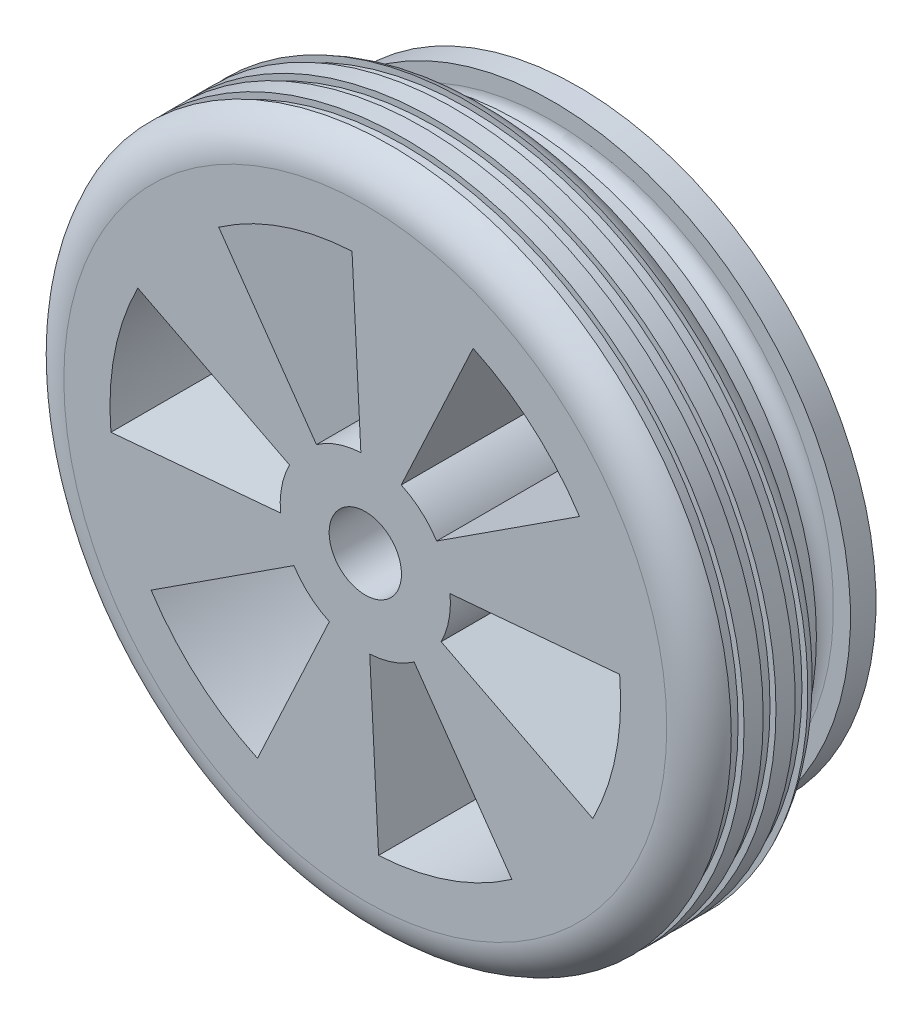
SolidWorks part; units mm, degrees
ref_plane "Plan de face" through (0, 0, 0) normal (0, 0, 1) x (1, 0, 0)
ref_plane "Plan de dessus" through (0, 0, 0) normal (0, 1, 0) x (1, 0, 0)
ref_plane "Plan de droite" through (0, 0, 0) normal (1, 0, 0) x (0, 0, -1)
sketch "Esquisse1" plane through (0, 0, 0) normal (0, 0, 1) x (1, 0, 0)
  circle A0 centre (0, 0) radius 40
  dimension "D1" = 80
extrude "Boss.-Extru.1" add sketch "Esquisse1" along normal blind 15
sketch "Esquisse2" plane through (0, 0, 0) normal (0, 0, -1) x (-1, 0, 0)
  circle A0 centre (0, 0) radius 9.65
  dimension "D1" = 19.3
extrude "Enlèv. mat.-Extru.1" cut sketch "Esquisse2" against normal blind 10.5
sketch "Esquisse3" plane through (0, 0, 10.5) normal (0, 0, -1) x (-1, 0, 0)
  circle A0 centre (0, 0) radius 4.25
  dimension "D1" = 8.5
extrude "Enlèv. mat.-Extru.2" cut sketch "Esquisse3" against normal up to next
ref_plane "Plan1" through (0, 0, 7.5) normal (0, 0, 1) x (1, 0, 0)
sketch "Esquisse4" plane through (0, 0, 7.5) normal (0, 0, 1) x (1, 0, 0)
  circle A0 centre (0, 0) radius 40
  circle A1 centre (0, 0) radius 40 construction
  circle A2 centre (0, 0) radius 39.3
  dimension "D1" = 78.6
extrude "Enlèv. mat.-Extru.4" cut sketch "Esquisse4" against normal blind 0.75 and the other way blind 0.75
ref_plane "Plan2" through (0, 0, 11.25) normal (0, 0, 1) x (1, 0, 0)
sketch "Esquisse5" plane through (0, 0, 11.25) normal (0, 0, 1) x (1, 0, 0)
  circle A1 centre (0, 0) radius 39.3
  circle A2 centre (0, 0) radius 39.3
  circle A3 centre (0, 0) radius 40
  circle A4 centre (0, 0) radius 40
  dimension "D1" = 0
  dimension "D2" = 0
extrude "Enlèv. mat.-Extru.5" cut sketch "Esquisse5" against normal blind 0.75 and the other way blind 0.75
ref_plane "Plan3" through (0, 0, 3.75) normal (0, 0, -1) x (-1, 0, 0)
sketch "Esquisse6" plane through (0, 0, 3.75) normal (0, 0, -1) x (-1, 0, 0)
  circle A1 centre (0, 0) radius 39.3
  circle A2 centre (0, 0) radius 39.3
  circle A3 centre (0, 0) radius 40
  circle A4 centre (0, 0) radius 40
  dimension "D1" = 0
  dimension "D2" = 0
extrude "Enlèv. mat.-Extru.6" cut sketch "Esquisse6" against normal blind 0.75 and the other way blind 0.75
fillet "Congé1" radius 5 2 edges at (40, 0, 0) (40, 0, 15)
sketch "Esquisse12" plane through (0, 0, 0) normal (0, 0, -1) x (-1, 0, 0)
  circle A0 centre (0, 0) radius 35
  dimension "D1" = 70
extrude "Boss.-Extru.8" add sketch "Esquisse12" along normal blind 10
sketch "Esquisse8" plane through (0, 0, 10.5) normal (0, 0, -1) x (-1, 0, 0)
  circle A0 centre (0, 0) radius 9.65
extrude "Boss.-Extru.2" add sketch "Esquisse8" along normal up to surface (10.5 mm away) up to face at (35, 0, 0)
sketch "Esquisse13" plane through (0, 0, 15) normal (0, 0, 1) x (1, 0, 0)
  circle A0 centre (0, 0) radius 4.25
extrude "Enlèv. mat.-Extru.10" cut sketch "Esquisse13" against normal up to surface (25 mm away) up to face at (-35, 0, -10)
sketch "Esquisse15" plane through (0, 0, -10) normal (0, 0, -1) x (-1, 0, 0)
  line L0 (0, 0) -> (-1.5592, -29.9595) construction
  line L1 (-1.5592, -29.9595) -> (0, 0) construction
  line L2 (0, 0) -> (-17.2184, -24.5668) construction
  line L3 (-1.5592, -29.9595) -> (-0.5197, -9.9865)
  line L4 (-17.2184, -24.5668) -> (-5.7395, -8.1889)
  line L5 (-26.7252, -13.6295) -> (-8.9084, -4.5432)
  line L6 (-29.8847, 2.6282) -> (-9.9616, 0.8761)
  line L7 (-25.1661, 16.33) -> (-8.3887, 5.4433)
  line L8 (-12.6662, 27.195) -> (-4.2221, 9.065)
  line L9 (1.5592, 29.9595) -> (0.5197, 9.9865)
  line L10 (17.2184, 24.5668) -> (5.7395, 8.1889)
  line L11 (26.7252, 13.6295) -> (8.9084, 4.5432)
  line L12 (29.8847, -2.6282) -> (9.9616, -0.8761)
  line L13 (25.1661, -16.33) -> (8.3887, -5.4433)
  line L14 (12.6662, -27.195) -> (4.2221, -9.065)
  circle A0 centre (0, 0) radius 10 construction
  circle A1 centre (0, 0) radius 30 construction
  arc A2 (-5.7395, -8.1889) -> (-0.5197, -9.9865) centre (0, 0) ccw
  arc A3 (-17.2184, -24.5668) -> (-1.5592, -29.9595) centre (0, 0) ccw
  arc A4 (-9.9616, 0.8761) -> (-8.9084, -4.5432) centre (0, 0) ccw
  arc A5 (-29.8847, 2.6282) -> (-26.7252, -13.6295) centre (0, 0) ccw
  arc A6 (-4.2221, 9.065) -> (-8.3887, 5.4433) centre (0, 0) ccw
  arc A7 (-12.6662, 27.195) -> (-25.1661, 16.33) centre (0, 0) ccw
  arc A8 (5.7395, 8.1889) -> (0.5197, 9.9865) centre (0, 0) ccw
  arc A9 (17.2184, 24.5668) -> (1.5592, 29.9595) centre (0, 0) ccw
  arc A10 (9.9616, -0.8761) -> (8.9084, 4.5432) centre (0, 0) ccw
  arc A11 (29.8847, -2.6282) -> (26.7252, 13.6295) centre (0, 0) ccw
  arc A12 (4.2221, -9.065) -> (8.3887, -5.4433) centre (0, 0) ccw
  arc A13 (12.6662, -27.195) -> (25.1661, -16.33) centre (0, 0) ccw
  point P31 (0, 0)
  dimension "D1" = 60
  dimension "D2" = 20
  dimension "D3" = 6
extrude "Enlèv. mat.-Extru.11" cut sketch "Esquisse15" against normal up to surface (25 mm away) up to face at (35.4174, 0, 15)
ref_plane "Plan4" through (0, 0, -5) normal (0, 0, -1) x (-1, 0, 0)
sketch "Esquisse16" plane through (0, 0, -5) normal (0, 0, -1) x (-1, 0, 0)
  circle A0 centre (0, 0) radius 31
  circle A1 centre (0, 0) radius 35 construction
  circle A2 centre (0, 0) radius 35
  dimension "D1" = 4
extrude "Enlèv. mat.-Extru.12" cut sketch "Esquisse16" against normal blind 2 and the other way blind 2
fillet "Congé2" radius 2 2 edges at (-31, 0, -7) (-31, 0, -3)
